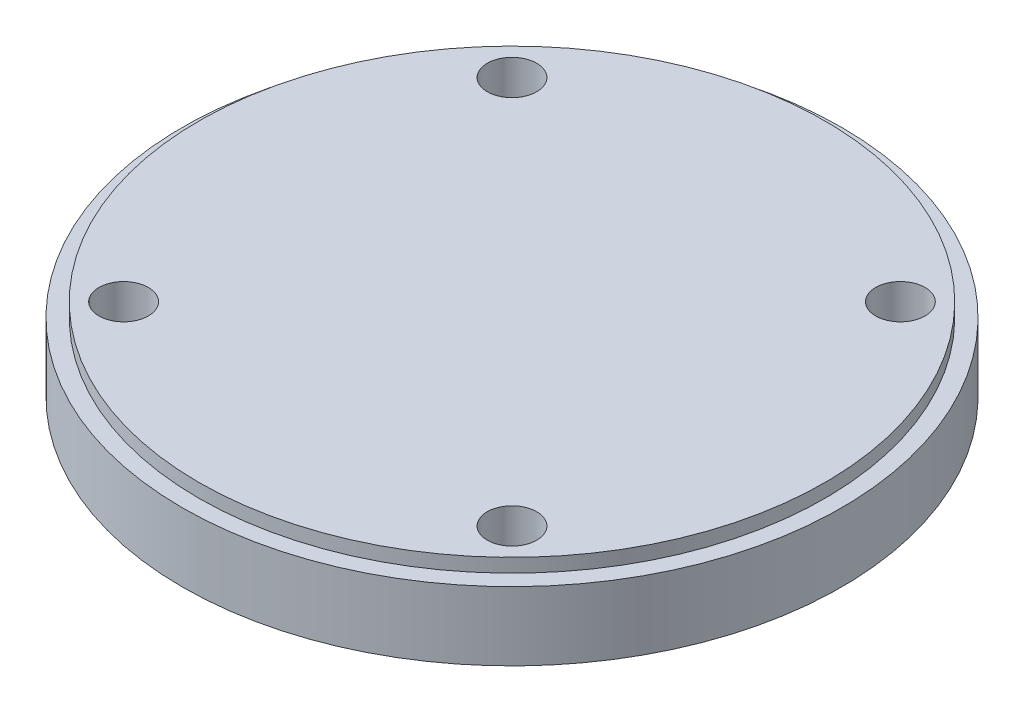
SolidWorks part; units mm, degrees
ref_plane "Front Plane" through (0, 0, 0) normal (0, 0, 1) x (1, 0, 0)
ref_plane "Top Plane" through (0, 0, 0) normal (0, 1, 0) x (1, 0, 0)
ref_plane "Right Plane" through (0, 0, 0) normal (1, 0, 0) x (0, 0, -1)
sketch "Sketch1" plane through (0, 0, 0) normal (0, 1, 0) x (1, 0, 0)
  circle A0 centre (0, 0) radius 57
  circle A1 centre (0, 0) radius 60
  dimension "D1" = 120
  dimension "D2" = 114
extrude "Extrude4" add sketch "Sketch1" along normal mid plane 15 contours A0
extrude "Extrude5" add sketch "Sketch" against normal up to surface (7.5 mm away) and the other way blind 5 up to face at (0, -7.5, 57)
sketch "Sketch" plane through (0, 0, 0) normal (0, 1, 0) x (1, 0, 0) same geometry as "Sketch1"
ref_axis "Axis1" through (0, 8.25, 0) along (0, -1, 0)
hole_wizard "M8 Clearance Hole3" positions "Sketch6" profile "Sketch7" hole size "M8" standard "ISO" end condition through all
sketch "Sketch6" plane through (0, 7.5, 0) normal (0, 1, 0) x (1, 0, 0)
  line L0 (-707.1068, -707.1068) -> (34648.2323, 34648.2323) construction
  line L1 (0, -8.25) -> (0, 8.25) construction
  point P0 (-35.3553, -35.3553)
  dimension "D1" = 50
  dimension "D2" = 45
sketch "Sketch7" plane through (-35.3553, 7.5, 35.3553) normal (1, 0, 0) x (0, 0, 1)
  line L0 (0, 0) -> (0, 15)
  line L1 (0, 15) -> (4.5, 15)
  line L2 (4.5, 15) -> (4.5, 0)
  line L5 (4.5, 0) -> (0, 0)
  line L11 (0, -6.35) -> (0, 107.95) construction
  dimension "Thru Hole Dia." = 9
  dimension "Thru Hole Depth" = 15
pattern_circular "CirPattern1" count 4 over 360 about axis through (0, 8.25, 0) along (0, -1, 0) of "M8 Clearance Hole3"
